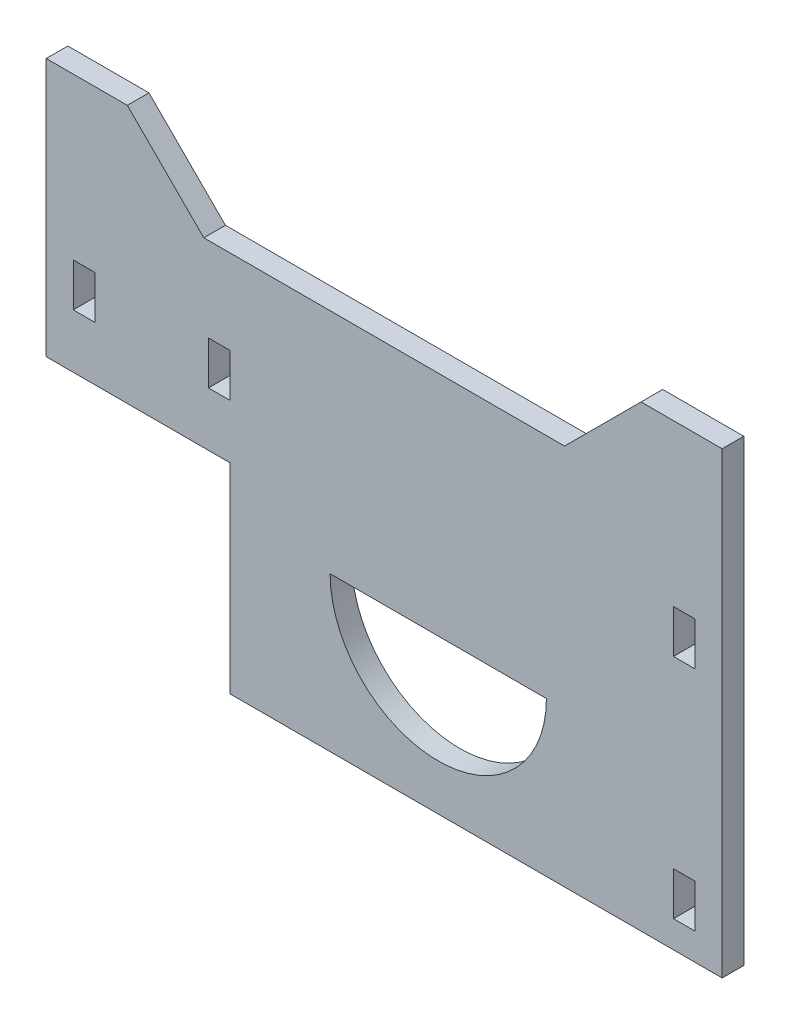
SolidWorks part; units mm, degrees
ref_plane "Front Plane" through (0, 0, 0) normal (0, 0, 1) x (1, 0, 0)
ref_plane "Top Plane" through (0, 0, 0) normal (0, 1, 0) x (1, 0, 0)
ref_plane "Right Plane" through (0, 0, 0) normal (1, 0, 0) x (0, 0, -1)
sketch "Sketch1" plane through (0, 0, 0) normal (0, 0, 1) x (1, 0, 0)
  line L0 (-20, -1.4984) -> (20, -1.4984)
  line L6 (-42.5, 25) -> (-38.5, 25)
  line L9 (-42.5, 25) -> (-42.5, 17)
  line L12 (-42.5, 17) -> (-38.5, 17)
  line L15 (-38.5, 25) -> (-38.5, 17)
  line L21 (-72.5, 30) -> (-72.5, 7)
  line L26 (-72.5, 7) -> (-38.5, 7)
  line L51 (52.5, 30) -> (52.5, -30)
  line L54 (43.5, 25) -> (47.5, 25)
  line L55 (43.5, 25) -> (43.5, 17)
  line L56 (43.5, 17) -> (47.5, 17)
  line L57 (47.5, 25) -> (47.5, 17)
  line L58 (47.5, -17) -> (43.5, -17)
  line L59 (47.5, -17) -> (47.5, -25)
  line L60 (47.5, -25) -> (43.5, -25)
  line L61 (43.5, -17) -> (43.5, -25)
  line L65 (-67.5, 25) -> (-63.5, 25)
  line L66 (-67.5, 25) -> (-67.5, 17)
  line L67 (-67.5, 17) -> (-63.5, 17)
  line L68 (-63.5, 25) -> (-63.5, 17)
  line L73 (-72.5, 30) -> (-72.5, -30) construction
  line L75 (-72.5, -30) -> (52.5, -30) construction
  line L76 (52.5, 30) -> (-72.5, 30)
  line L77 (-38.5, 7) -> (-38.5, -30)
  line L78 (-38.5, -30) -> (52.5, -30)
  arc A12 (-20, -1.4984) -> (20, -1.4984) centre (0, -1.4984) ccw
  point P0 (0, 0)
  point P4 (-65.5, 17)
  point P13 (-38.5, 21)
  point P25 (-63.5, 21)
  dimension "D3" = 4
  dimension "D4" = 8
  dimension "D5" = 21
  dimension "D6" = 60
  dimension "D7" = 10
  dimension "D2" = 82
  dimension "D8" = 20
  dimension "D9" = 20
  dimension "D10" = 0
  dimension "D13" = 5
  dimension "D14" = 5
  dimension "D18" = 5
extrude "Boss-Extrude1" add sketch "Sketch1" along normal blind 4
sketch "Sketch2" plane through (0, 0, 0) normal (0, 0, 1) x (1, 0, 0)
  line L0 (-72.5, 30) -> (52.5, 30)
  line L4 (23.3579, 40.6191) -> (-43.3579, 40.6191)
  line L5 (-43.3579, 40.6191) -> (-57.5, 54.7612)
  line L6 (-57.5, 54.7612) -> (-72.5, 54.7612)
  line L7 (-72.5, 54.7612) -> (-72.5, 30)
  line L8 (23.3579, 40.6191) -> (37.5, 54.7612)
  line L9 (37.5, 54.7612) -> (52.5, 54.7612)
  line L10 (52.5, 54.7612) -> (52.5, 30)
  dimension "D1" = 24.7612
  dimension "D2" = 20
  dimension "D3" = 15
  dimension "D4" = 135
extrude "Boss-Extrude2" add sketch "Sketch2" along normal blind 4
